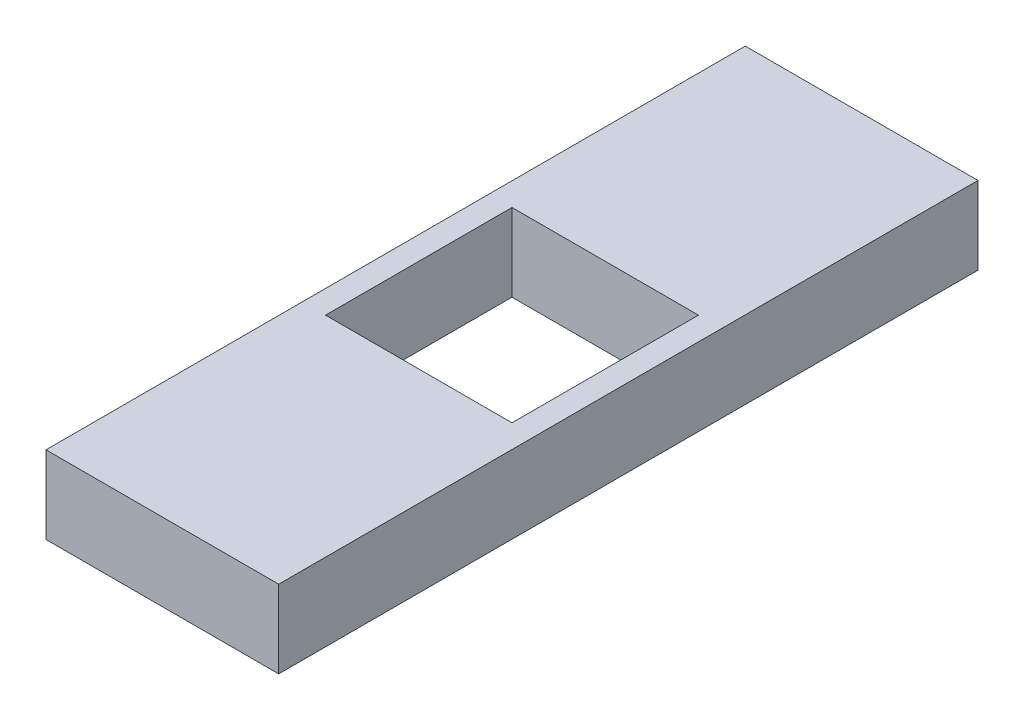
SolidWorks part; units mm, degrees
material "Polyurethane Foam Rigid"
ref_plane "X-Y Datum" through (0, 0, 0) normal (0, 0, 1) x (1, 0, 0)
ref_plane "X-Z Datum" through (0, 0, 0) normal (0, 1, 0) x (1, 0, 0)
ref_plane "Y-Z Datum" through (0, 0, 0) normal (1, 0, 0) x (0, 0, -1)
sketch "Sketch1" plane through (0, 0, 0) normal (0, 0, 1) x (1, 0, 0)
  line L1 (-38.0378, -12.7) -> (38.0378, -12.7)
  line L2 (-38.0378, -12.7) -> (-38.0378, 12.7)
  line L3 (-38.0378, 12.7) -> (38.0378, 12.7)
  line L4 (38.0378, -12.7) -> (38.0378, 12.7)
  line L5 (-38.0378, -12.7) -> (38.0378, 12.7) construction
  line L6 (-38.0378, 12.7) -> (38.0378, -12.7) construction
  point P0 (0, 0)
  dimension "D1" = 25.4
  dimension "D2" = 76.0755
extrude "Boss-Extrude1" add sketch "Sketch1" along normal blind 228.6
sketch "Sketch2" plane through (0, -12.7, 0) normal (0, -1, 0) x (1, 0, 0)
  line L0 (0, 0) -> (0, 228.6) construction
  line L1 (-38.0378, 228.6) -> (38.0378, 228.6) construction
  line L3 (-30.48, 144.78) -> (30.48, 144.78)
  line L4 (-30.48, 144.78) -> (-30.48, 83.82)
  line L5 (-30.48, 83.82) -> (30.48, 83.82)
  line L6 (30.48, 144.78) -> (30.48, 83.82)
  line L7 (-30.48, 144.78) -> (30.48, 83.82) construction
  line L8 (-30.48, 83.82) -> (30.48, 144.78) construction
  point P5 (0, 114.3)
  dimension "D1" = 60.96
  dimension "D2" = 60.96
extrude "Cut-Extrude1" cut sketch "Sketch2" against normal through all
